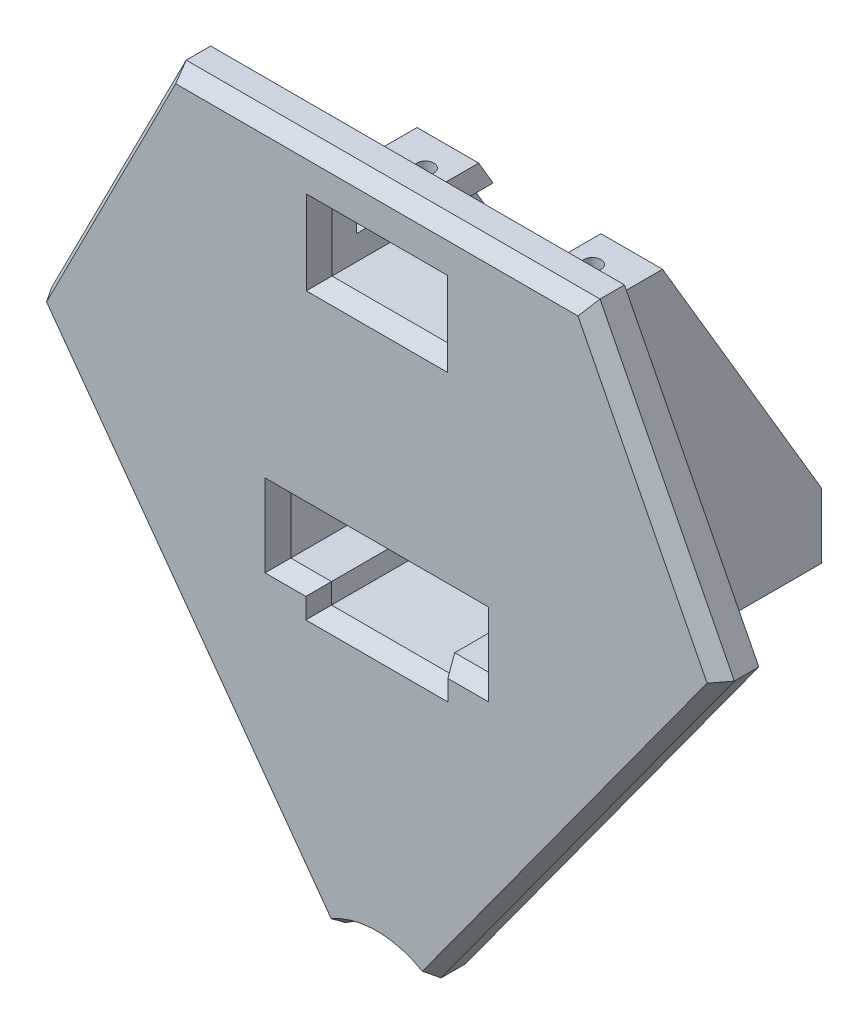
SolidWorks part; units mm, degrees
ref_plane "Front Plane" through (0, 0, 0) normal (0, 0, 1) x (1, 0, 0)
ref_plane "Top Plane" through (0, 0, 0) normal (0, 1, 0) x (1, 0, 0)
ref_plane "Right Plane" through (0, 0, 0) normal (1, 0, 0) x (0, 0, -1)
sketch "Sketch2" plane through (0, 0, 0) normal (0, 1, 0) x (1, 0, 0)
  line L0 (15.061, 0) -> (15.061, 32)
  line L1 (-12.561, 2.5) -> (12.561, 2.5)
  line L2 (-12.561, 2.5) -> (-12.561, 32)
  line L4 (12.561, 2.5) -> (12.561, 32)
  line L5 (15.061, 32) -> (12.561, 32)
  line L7 (-15.061, 32) -> (-15.061, 0)
  line L8 (-15.061, 0) -> (15.061, 0)
  line L10 (-15.061, 32) -> (-12.561, 32)
  point P4 (0, 2.5)
  point P12 (0, 0)
  dimension "D1" = 2.5
  dimension "D2" = 2.5
  dimension "D3" = 29.5
  dimension "D4" = 25.122
extrude "Boss-Extrude1" add sketch "Sketch2" along normal blind 32.5
sketch "Sketch4" plane through (0, 0, 0) normal (0, -1, 0) x (1, 0, 0)
  line L10 (-7.561, -6) -> (-7.561, 0)
  line L13 (-12.561, -2.5) -> (-12.561, -32) construction
  line L18 (-12.561, -10) -> (-7.561, -6)
  line L23 (12.561, -32) -> (12.561, -2.5) construction
  line L26 (12.561, -10) -> (7.561, -6)
  line L33 (-15.061, -32) -> (-15.061, 0) construction
  line L36 (15.061, 0) -> (15.061, -32) construction
  line L38 (-7.561, 0) -> (-15.061, 0)
  line L39 (7.561, -6) -> (7.561, 0)
  line L40 (7.561, 0) -> (15.061, 0)
  line L41 (-15.061, 0) -> (-15.061, -32)
  line L42 (-15.061, -32) -> (-12.561, -32)
  line L43 (-12.561, -32) -> (-15.061, -32) construction
  line L44 (-12.561, -32) -> (-12.561, -10)
  line L45 (12.561, -10) -> (12.561, -32)
  line L46 (12.561, -32) -> (15.061, -32)
  line L47 (15.061, -32) -> (15.061, 0)
  circle A2 centre (-10.2499, -4.95) radius 1.05
  circle A5 centre (10.2499, -4.95) radius 1.05
  dimension "D4" = 6
  dimension "D5" = 2.1
  dimension "D1" = 7.5
  dimension "D2" = 7.5
  dimension "D3" = 10
extrude "Boss-Extrude2" add sketch "Sketch4" along normal blind 2.5
sketch "Sketch5" plane through (0, 32.5, 0) normal (0, 1, 0) x (1, 0, 0)
  line L0 (-15.061, 32) -> (-10.2499, 32)
  line L9 (-10.2499, 32) -> (-6.25, 26)
  line L13 (-15.061, 0) -> (15.061, 0) construction
  line L14 (15.061, 0) -> (-15.061, 0)
  line L15 (-15.061, 0) -> (-15.061, 32)
  line L20 (15.061, 0) -> (15.061, 32)
  line L21 (-6.25, 26) -> (6.25, 26)
  line L22 (6.25, 26) -> (10.2499, 32)
  line L23 (10.2499, 32) -> (15.061, 32)
  circle A0 centre (-10.2499, 4.95) radius 1.05 construction
  circle A1 centre (-10.2499, 8.7) radius 1.05
  circle A2 centre (10.2499, 8.7) radius 1.05
  point P6 (0, 26)
  dimension "D4" = 0
  dimension "D1" = 8.7
  dimension "D2" = 12.5
  dimension "D3" = 20.4998
  dimension "D5" = 6
extrude "Boss-Extrude3" add sketch "Sketch5" along normal blind 3
sketch "Sketch6" plane through (-15.061, 0, 0) normal (-1, 0, 0) x (0, 0, 1)
  line L0 (-12.5, 35.5) -> (-32, 2.5)
  line L1 (-32, 2.5) -> (-32, 35.5)
  line L2 (-32, 35.5) -> (-12.5, 35.5)
  line L3 (-32, 35.5) -> (-32, -2.5) construction
  line L4 (-32, 35.5) -> (0, 35.5) construction
  line L6 (0, -2.5) -> (-32, -2.5) construction
  line L7 (0, 35.5) -> (0, -2.5) construction
  dimension "D1" = 5
  dimension "D2" = 12.5
extrude "Cut-Extrude1" cut sketch "Sketch6" against normal through all
ref_plane "Plane1" through (0, 16.5, 0) normal (0, -1, 0) x (-1, 0, 0)
sketch "Sketch13" plane through (0, 0, 0) normal (0, 0, 1) x (1, 0, 0)
  line L1 (-15.061, 35.5) -> (15.061, 35.5)
  line L2 (-15.061, 35.5) -> (-15.061, -2.5)
  line L3 (-15.061, -2.5) -> (15.061, -2.5)
  line L4 (15.061, 35.5) -> (15.061, -2.5)
extrude "Boss-Extrude7" add sketch "Sketch13" along normal blind 2.5
sketch "Sketch8" plane through (0, 0, 2.5) normal (0, 0, 1) x (1, 0, 0)
  line L0 (0, -43.5) -> (-43.5926, 16.5)
  line L1 (-16.5671, 16.5) -> (16.5671, 16.5) construction
  line L2 (-43.5926, 16.5) -> (43.5926, 16.5)
  line L3 (43.5926, 16.5) -> (0, -43.5)
  dimension "D1" = 72
  dimension "D2" = 60
extrude "Boss-Extrude4" add sketch "Sketch8" along normal blind 5
sketch "Sketch9" plane through (0, 0, 2.5) normal (0, 0, 1) x (1, 0, 0)
  line L0 (43.5926, 16.5) -> (65.3888, 46.5)
  line L1 (65.3888, 46.5) -> (-65.3888, 46.5)
  line L2 (-65.3888, 46.5) -> (-43.5926, 16.5)
  line L3 (43.5926, 16.5) -> (-43.5926, 16.5)
  line L4 (0, -43.5) -> (43.5926, 16.5) construction
  line L5 (-43.5926, 16.5) -> (0, -43.5) construction
  dimension "D1" = 30
extrude "Boss-Extrude6" add sketch "Sketch9" along normal up to surface (5 mm away) up to face at (0, -3.5, 7.5)
sketch "Sketch10" plane through (0, 0, 2.5) normal (0, 0, -1) x (-1, 0, 0)
  line L25 (-25.3888, 46.5) -> (-65.3888, 46.5)
  line L26 (-65.3888, 46.5) -> (65.3888, 46.5) construction
  line L27 (-65.3888, 46.5) -> (-41.8774, 14.1393)
  line L28 (0, -43.5) -> (-65.3888, 46.5) construction
  line L29 (-41.8774, 14.1393) -> (-25.3888, 46.5)
  line L30 (65.3888, 46.5) -> (41.8774, 14.1393)
  line L31 (65.3888, 46.5) -> (0, -43.5) construction
  line L32 (41.8774, 14.1393) -> (25.3888, 46.5)
  line L33 (25.3888, 46.5) -> (65.3888, 46.5)
  dimension "D1" = 40
extrude "Cut-Extrude2" cut sketch "Sketch10" against normal through all
sketch "Sketch14" plane through (0, 0, -2.5) normal (0, 0, -1) x (-1, 0, 0)
  line L11 (-7.561, -2.5) -> (7.561, -2.5)
  line L12 (15.061, -2.5) -> (-15.061, -2.5) construction
  line L13 (7.561, -2.5) -> (7.561, 0)
  line L14 (12.561, 0) -> (7.561, 0) construction
  line L15 (7.561, -2.5) -> (7.561, 0) construction
  line L16 (7.561, 0) -> (12.561, 0)
  line L17 (12.561, 0) -> (12.561, 7.7837)
  line L18 (12.561, 2.5) -> (12.561, 32.5) construction
  line L19 (12.561, 7.7837) -> (-12.561, 7.7837)
  line L20 (-12.561, 32.5) -> (-12.561, 2.5) construction
  line L21 (-12.561, 7.7837) -> (-12.561, 0)
  line L22 (-12.561, 2.5) -> (-12.561, -2.5) construction
  line L23 (-7.561, 0) -> (-12.561, 0) construction
  line L24 (-12.561, 0) -> (-7.561, 0)
  line L25 (-7.561, 0) -> (-7.561, -2.5)
  line L26 (-7.561, -2.5) -> (-12.561, -2.5) construction
  line L27 (-15.061, 35.5) -> (15.061, 35.5) construction
  line L28 (-7.5, 35.5) -> (7.5, 35.5)
  line L29 (-7.5, 35.5) -> (-7.5, 40.5)
  line L30 (-7.5, 40.5) -> (7.5, 40.5)
  line L31 (7.5, 35.5) -> (7.5, 40.5)
  point P37 (0, 35.5)
  dimension "D1" = 15
  dimension "D2" = 5
extrude "Cut-Extrude3" cut sketch "Sketch14" against normal through all
sketch "Sketch15" plane through (0, -2.5, 0) normal (0, -1, 0) x (1, 0, 0)
  line L1 (15.061, -32) -> (-15.061, -32)
  line L2 (15.061, -32) -> (15.061, 2.5)
  line L3 (15.061, 2.5) -> (-15.061, 2.5)
  line L4 (-15.061, -32) -> (-15.061, 2.5)
  circle A0 centre (-10.2499, -4.95) radius 2.495
  circle A1 centre (10.341, -4.95) radius 2.495
  dimension "D1" = 4.99
  dimension "D2" = 4.99
extrude "Boss-Extrude8" add sketch "Sketch15" along normal blind 3
sketch "Sketch17" plane through (0, -5.5, 0) normal (0, -1, 0) x (1, 0, 0)
  line L0 (15.061, 2.5) -> (-15.061, 2.5) construction
  circle A0 centre (0, -37.5) radius 13.75
  dimension "D2" = 27.5
  dimension "D1" = 40
extrude "Cut-Extrude4" cut sketch "Sketch17" against normal through all
sketch "Sketch19" plane through (0, 0, -2.5) normal (0, 0, -1) x (-1, 0, 0)
  line L0 (-15.061, 35.5) -> (15.061, 35.5) construction
  line L1 (7.5, 35.5) -> (-7.5, 35.5)
  line L2 (7.5, 35.5) -> (7.5, 32.5)
  line L3 (7.5, 32.5) -> (-7.5, 32.5)
  line L4 (-7.5, 35.5) -> (-7.5, 32.5)
  line L5 (7.5, 35.5) -> (7.5, 40.5) construction
  line L6 (-7.5, 40.5) -> (-7.5, 35.5) construction
  line L7 (-12.561, 32.5) -> (12.561, 32.5) construction
  dimension "D1" = 0
  dimension "D2" = 0
  dimension "D3" = 0
extrude "Cut-Extrude6" cut sketch "Sketch19" along normal through all both and the other way through all
ref_axis "Axis1" through (0, -43.5, 11.5724) along (0, 0, -1)
sketch "Sketch20" plane through (0, 0, 2.5) normal (0, 0, -1) x (-1, 0, 0)
  circle A0 centre (0, -43.5) radius 10
  dimension "D1" = 20
extrude "Cut-Extrude7" cut sketch "Sketch20" against normal through all
chamfer "Chamfer1" distance 2 angle 30 18 edges at (-23.8776, -10.6353, 7.5) (-33.6331, 30.3197, 7.5) (0, 46.5, 7.5) (33.6331, 30.3197, 7.5) (23.8776, -10.6353, 7.5) (7.5, 36.5, 7.5) (0, 40.5, 7.5) (-7.5, 36.5, 7.5) (0, 32.5, 7.5) (12.561, 3.8918, 7.5) (0, 7.7837, 7.5) (-12.561, 3.8918, 7.5) (-10.061, 0, 7.5) (-7.561, -1.25, 7.5) (0, -2.5, 7.5) (7.561, -1.25, 7.5) (10.061, 0, 7.5) (0, -33.5, 7.5) first distance on face at (-23.8776, -10.6353, 5) first distance on face at (-33.6331, 30.3197, 5) first distance on face at (0, 46.5, 5) first distance on face at (33.6331, 30.3197, 5) first distance on face at (23.8776, -10.6353, 5) first distance on face at (7.5, 35.6429, -1.3247) first distance on face at (0, 40.5, 5) first distance on face at (-7.5, 35.6429, -1.3247) first distance on face at (0, 32.5, 2.5) first distance on face at (12.561, 8.6917, -9.7874) first distance on face at (0, 7.7837, 2.5) first distance on face at (-12.561, 8.6917, -9.7874) first distance on face at (-10.061, 0, -0.25) first distance on face at (-7.561, -1.25, 0.75) first distance on face at (0, -2.5, -9.0821) first distance on face at (7.561, -1.25, 0.75) first distance on face at (10.061, 0, -0.25) first distance on face at (0, -34.4549, 5)
